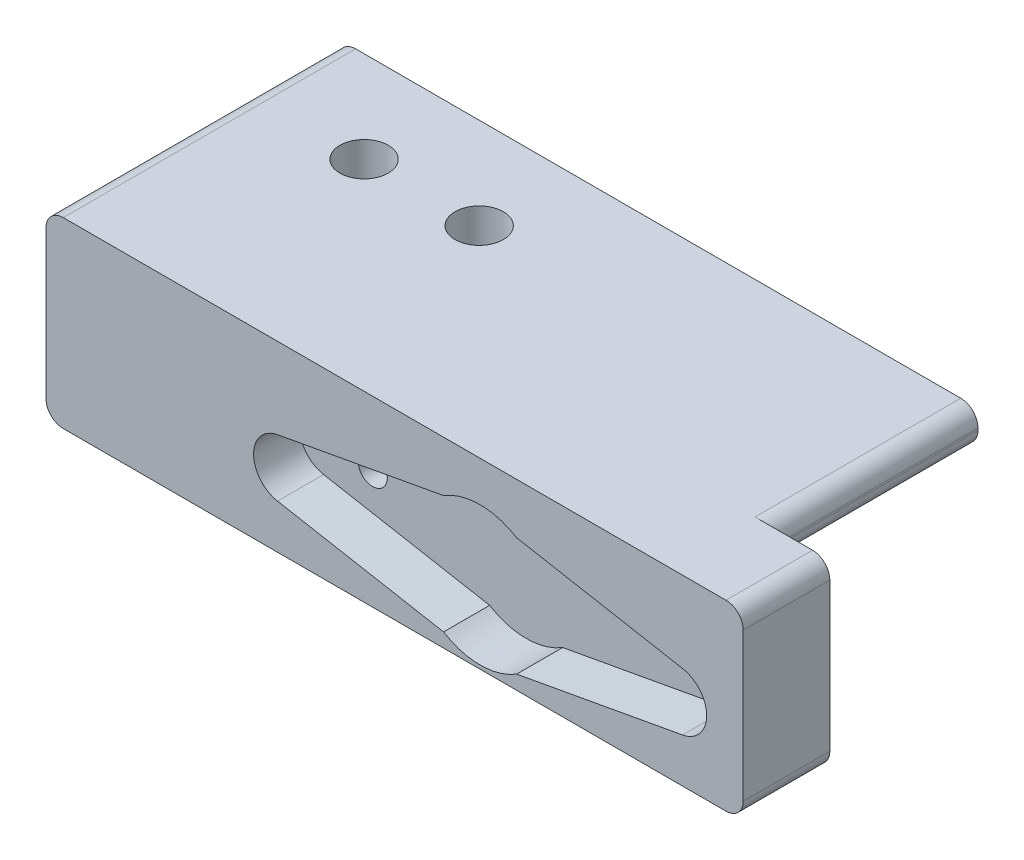
SolidWorks part; units mm, degrees
ref_plane "Front Plane" through (0, 0, 0) normal (0, 0, 1) x (1, 0, 0)
ref_plane "Top Plane" through (0, 0, 0) normal (0, 1, 0) x (1, 0, 0)
ref_plane "Right Plane" through (0, 0, 0) normal (1, 0, 0) x (0, 0, -1)
sketch "Sketch1" plane through (0, 0, 0) normal (0, 0, 1) x (1, 0, 0)
  line L1 (-37.719, -6.35) -> (37.719, -6.35)
  line L2 (-37.719, -6.35) -> (-37.719, 6.35)
  line L3 (-37.719, 6.35) -> (37.719, 6.35)
  line L4 (37.719, -6.35) -> (37.719, 6.35)
  line L5 (0, 6.35) -> (0, -6.35) construction
  line L6 (-37.719, 0) -> (37.719, 0) construction
  point P0 (0, 0)
  dimension "D1" = 75.438
  dimension "D2" = 12.7
extrude "Boss-Extrude1" add sketch "Sketch1" along normal blind 6.35
sketch "Sketch2" plane through (0, 0, 6.35) normal (0, 0, 1) x (1, 0, 0)
  line L1 (0, 0) -> (3.175, 5.1294) construction
  line L2 (0, -1000) -> (0, 49000) construction
  line L3 (3.175, 5.1294) -> (17.6007, 2.4988)
  line L4 (-1000, 0) -> (49000, 0) construction
  line L5 (3.175, -5.1294) -> (17.6007, -2.4988)
  line L6 (-3.175, -5.1294) -> (-17.6007, -2.4988)
  line L7 (-3.175, 5.1294) -> (-17.6007, 2.4988)
  arc A0 (-3.175, -5.1294) -> (3.175, -5.1294) centre (0, 0) ccw
  arc A1 (17.6007, -2.4988) -> (17.6007, 2.4988) centre (17.145, 0) ccw
  arc A2 (-17.6007, -2.4988) -> (-17.6007, 2.4988) centre (-17.145, 0) cw
  arc A3 (3.175, 5.1294) -> (-3.175, 5.1294) centre (0, 0) ccw
  dimension "D1" = 12.065
  dimension "D2" = 5.08
  dimension "D3" = 17.145
  dimension "D4" = 3.175
extrude "Cut-Extrude1" cut sketch "Sketch2" against normal blind 4
sketch "Sketch3" plane through (0, 0, 0) normal (0, 1, 0) x (1, 0, 0)
  line L0 (-34.544, 3.175) -> (34.544, 3.175)
  line L1 (-37.719, 0) -> (37.719, 0)
  line L2 (-37.719, 0) -> (-37.719, 19.05)
  line L3 (-37.719, 19.05) -> (37.719, 19.05)
  line L4 (37.719, 0) -> (37.719, 19.05)
  line L5 (34.544, 3.175) -> (34.544, 15.875)
  line L6 (-34.544, 15.875) -> (34.544, 15.875)
  line L7 (-34.544, 3.175) -> (-34.544, 15.875)
  dimension "D2" = 19.05
  dimension "D1" = 3.175
extrude "Boss-Extrude2" add sketch "Sketch3" along normal up to surface and the other way up to surface up to face at (0, 6.35, 3.175) other way up to face at (0, -6.35, 3.175)
sketch "Sketch4" plane through (0, 6.35, 0) normal (0, 1, 0) x (1, 0, 0)
  line L0 (-37.719, -6.35) -> (-37.719, 19.05) construction
  line L1 (-37.719, -6.35) -> (37.719, -6.35)
  line L2 (-37.719, -6.35) -> (-37.719, 19.05)
  line L3 (-37.719, 19.05) -> (37.719, 19.05)
  line L4 (37.719, -6.35) -> (37.719, 19.05)
extrude "Boss-Extrude4" add sketch "Sketch4" along normal blind 3.175
sketch "Sketch7" plane through (0, 0, 6.35) normal (0, 0, 1) x (1, 0, 0)
  line L0 (-37.719, 9.525) -> (37.719, 9.525) construction
  line L1 (37.719, -6.35) -> (22.86, -6.35)
  line L2 (37.719, -6.35) -> (37.719, 9.525)
  line L3 (37.719, 9.525) -> (22.86, 9.525)
  line L4 (22.86, -6.35) -> (22.86, 9.525)
  arc A0 (17.6007, -2.4988) -> (17.6007, 2.4988) centre (17.145, 0) ccw construction
  point P10 (19.685, 0)
  dimension "D1" = 3.175
extrude "Cut-Extrude3" cut sketch "Sketch7" against normal through all
sketch "Sketch8" plane through (22.86, 0, 0) normal (1, 0, 0) x (0, 0, -1)
  line L1 (15.875, -6.35) -> (19.05, -6.35)
  line L2 (15.875, -6.35) -> (15.875, 9.525)
  line L3 (15.875, 9.525) -> (19.05, 9.525)
  line L4 (19.05, -6.35) -> (19.05, 9.525)
extrude "Cut-Extrude4" cut sketch "Sketch8" against normal through all
sketch "Sketch9" plane through (0, 0, -15.875) normal (0, 0, -1) x (-1, 0, 0)
  line L6 (34.544, 6.35) -> (34.544, -6.35)
  line L7 (34.544, -6.35) -> (37.719, -6.35)
  line L8 (37.719, -6.35) -> (37.719, 9.525)
  line L9 (37.719, 9.525) -> (-22.86, 9.525)
  line L10 (-22.86, 9.525) -> (-22.86, 6.35)
  line L11 (-22.86, 6.35) -> (34.544, 6.35)
  line L12 (34.544, 6.35) -> (34.544, -6.35)
  line L13 (34.544, -6.35) -> (37.719, -6.35)
  line L14 (37.719, -6.35) -> (37.719, 9.525)
  line L15 (37.719, 9.525) -> (-22.86, 9.525)
  line L16 (-22.86, 9.525) -> (-22.86, 6.35)
  line L17 (-22.86, 6.35) -> (34.544, 6.35)
  dimension "D1" = 0
extrude "Boss-Extrude5" add sketch "Sketch9" along normal blind 3.175
sketch "Sketch10" plane through (0, 6.35, 0) normal (0, -1, 0) x (1, 0, 0)
  line L0 (-1034.544, -11.1125) -> (48965.456, -11.1125) construction
  line L1 (-34.544, -3.175) -> (-34.544, -19.05) construction
  line L2 (-1042.3688, -14.9275) -> (48957.6312, -14.9275) construction
  circle A0 centre (-27.544, -11.1125) radius 2.1
  circle A1 centre (-17.544, -11.1125) radius 2.1
  point P9 (-34.544, -11.1125)
  point P10 (-29.4406, -11.1125)
  point P12 (-24.6081, -11.1125)
  dimension "D3" = 4.2
  dimension "D4" = 4.2
  dimension "D1" = 10
  dimension "D2" = 7
sketch "Sketch11" plane through (0, 0, -3.175) normal (0, 0, -1) x (-1, 0, 0)
  line L1 (-22.86, 6.35) -> (34.544, 6.35)
  line L2 (-22.86, 6.35) -> (-22.86, -6.35)
  line L3 (-22.86, -6.35) -> (34.544, -6.35)
  line L4 (34.544, 6.35) -> (34.544, -6.35)
extrude "Cut-Extrude5" cut sketch "Sketch11" against normal blind 2
sketch "Sketch12" plane through (0, 0, 2.35) normal (0, 0, 1) x (1, 0, 0)
  line L0 (0, -1000) -> (0, 49000) construction
  circle A0 centre (13.335, 0) radius 1.27
  circle A1 centre (-13.335, 0) radius 1.27
  dimension "D1" = 2.54
  dimension "D2" = 13.335
extrude "Cut-Extrude6" cut sketch "Sketch12" against normal through all
extrude "Cut-Extrude7" cut sketch "Sketch10" against normal through all
sketch "Sketch13" plane through (22.86, 0, 0) normal (1, 0, 0) x (0, 0, -1)
  line L1 (1.175, 6.35) -> (19.05, 6.35)
  line L2 (1.175, 6.35) -> (1.175, 9.525)
  line L3 (1.175, 9.525) -> (19.05, 9.525)
  line L4 (19.05, 6.35) -> (19.05, 9.525)
extrude "Cut-Extrude8" cut sketch "Sketch13" against normal blind 5
fillet "Fillet2" radius 1.5 8 edges at (-37.719, 9.525, -6.35) (-34.544, 6.35, -10.1125) (-37.719, -6.35, -6.35) (-34.544, -6.35, -10.1125) (22.86, 9.525, 2.5875) (22.86, -6.35, 2.5875) (17.86, 9.525, -10.1125) (17.86, 6.35, -10.1125)
